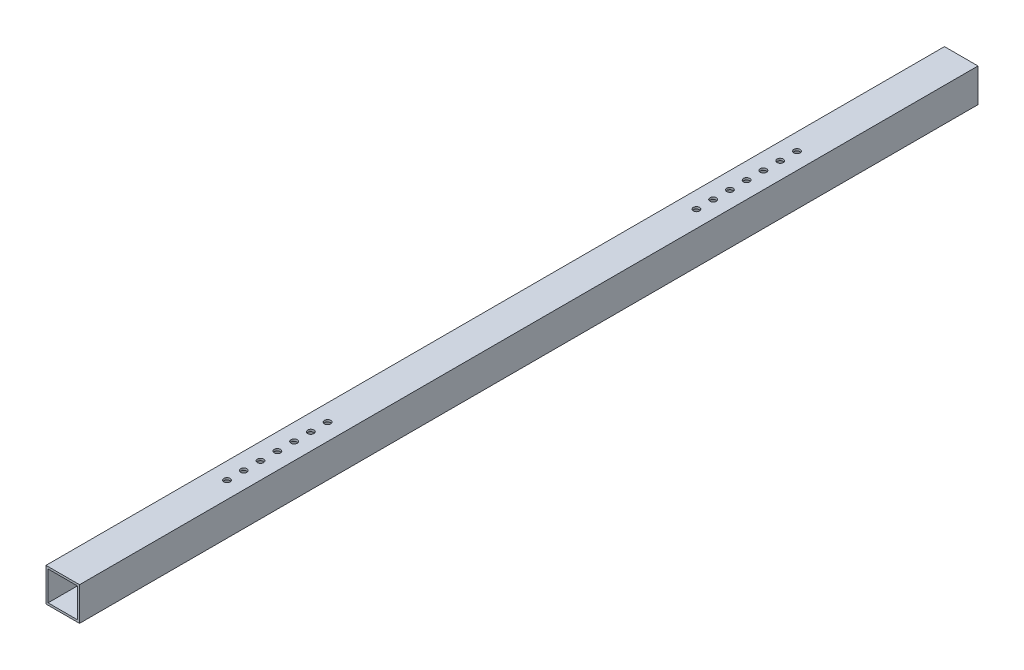
SolidWorks part; units mm, degrees
material "ALUMINUM 6061-T6"
ref_plane "Front Plane" through (0, 0, 0) normal (0, 0, 1) x (1, 0, 0)
ref_plane "Top Plane" through (0, 0, 0) normal (0, 1, 0) x (1, 0, 0)
ref_plane "Right Plane" through (0, 0, 0) normal (1, 0, 0) x (0, 0, -1)
sketch "Sketch1" plane through (0, 0, 0) normal (0, 0, 1) x (1, 0, 0)
  line L1 (-12.7, -12.7) -> (12.7, -12.7)
  line L2 (-12.7, -12.7) -> (-12.7, 12.7)
  line L3 (-12.7, 12.7) -> (12.7, 12.7)
  line L4 (12.7, -12.7) -> (12.7, 12.7)
  line L5 (-12.7, -12.7) -> (12.7, 12.7) construction
  line L6 (-12.7, 12.7) -> (12.7, -12.7) construction
  point P0 (0, 0)
  dimension "D1" = 25.4
  dimension "D2" = 25.4
extrude "Boss-Extrude1" add sketch "Sketch1" along normal mid plane 680.72
sketch "Sketch2" plane through (0, 0, 340.36) normal (0, 0, 1) x (1, 0, 0)
  line L0 (-11.1125, 11.1125) -> (-11.1125, -11.1125)
  line L1 (-12.7, 12.7) -> (12.7, 12.7)
  line L2 (-12.7, 12.7) -> (-12.7, -12.7)
  line L3 (-12.7, -12.7) -> (12.7, -12.7)
  line L4 (12.7, 12.7) -> (12.7, -12.7)
  line L5 (-11.1125, -11.1125) -> (11.1125, -11.1125)
  line L6 (11.1125, 11.1125) -> (11.1125, -11.1125)
  line L7 (-11.1125, 11.1125) -> (11.1125, 11.1125)
  dimension "D1" = 1.5875
extrude "Cut-Extrude1" cut sketch "Sketch2" against normal through all contours L7 L6 L5 L0
sketch "Sketch3" plane through (0, 12.7, 0) normal (0, 1, 0) x (1, 0, 0)
  line L1 (-12.7, -340.36) -> (-12.7, 340.36) construction
  circle A0 centre (0, -215.9) radius 2.3812
  circle A1 centre (0, -203.2) radius 2.3812
  circle A2 centre (0, -190.5) radius 2.3812
  circle A3 centre (0, -177.8) radius 2.3812
  circle A4 centre (0, -165.1) radius 2.3812
  circle A5 centre (0, -152.4) radius 2.3812
  circle A6 centre (0, -139.7) radius 2.3812
  circle A7 centre (0, 139.7) radius 2.3812
  circle A8 centre (0, 152.4) radius 2.3812
  circle A9 centre (0, 165.1) radius 2.3812
  circle A10 centre (0, 177.8) radius 2.3812
  circle A11 centre (0, 190.5) radius 2.3812
  circle A12 centre (0, 215.9) radius 2.3813
  circle A13 centre (0, 203.2) radius 2.3812
  point P29 (0, 177.8)
  point P32 (-12.7, 0)
  point P33 (0, -177.8)
  dimension "D1" = 4.7625
  dimension "D2" = 12.7
  dimension "D3" = 12.7
  dimension "D4" = 12.7
  dimension "D5" = 12.7
  dimension "D6" = 12.7
  dimension "D7" = 12.7
  dimension "D8" = 4.7625
  dimension "D9" = 12.7
  dimension "D10" = 12.7
  dimension "D12" = 12.7
  dimension "D13" = 12.7
  dimension "D14" = 12.7
  dimension "D16" = 177.8
  dimension "D11" = 12.7
  dimension "D15" = 355.6
extrude "Cut-Extrude2" cut sketch "Sketch3" against normal through all
sketch3d "3DSketch1"
